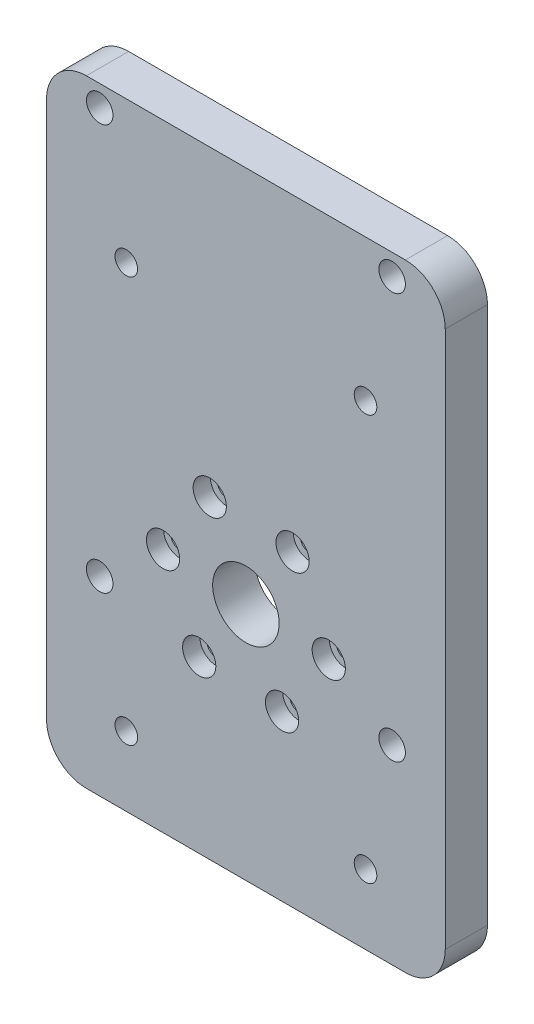
SolidWorks part; units mm, degrees
material "Aleación 6061"
ref_plane "Alzado" through (0, 0, 0) normal (0, 0, 1) x (1, 0, 0)
ref_plane "Planta" through (0, 0, 0) normal (0, 1, 0) x (1, 0, 0)
ref_plane "Vista lateral" through (0, 0, 0) normal (1, 0, 0) x (0, 0, -1)
ref_plane "Plano_xJ3" through (152.4, 0, 0) normal (1, 0, 0) x (0, 0, -1)
ref_plane "Plano_zJ5" through (0, 0, 336.55) normal (0, 0, 1) x (1, 0, 0)
ref_axis "Eje_J4" through (152.4, 0, 276.2675) along (0, 0, -1)
ref_axis "Eje_J5" through (152.4, -19.6438, 336.55) along (0, 1, 0)
sketch "Croquis13" plane through (0, 0, 0) normal (0, 0, 1) x (1, 0, 0)
  line L0 (128.4, -36) -> (176.4, -36)
  line L1 (182.4, -30) -> (182.4, 50.875)
  line L2 (176.4, 56.875) -> (128.4, 56.875)
  line L3 (122.4, 50.875) -> (122.4, -30)
  arc A0 (176.4, -36) -> (182.4, -30) centre (176.4, -30) ccw
  arc A1 (182.4, 50.875) -> (176.4, 56.875) centre (176.4, 50.875) ccw
  arc A2 (128.4, 56.875) -> (122.4, 50.875) centre (128.4, 50.875) ccw
  arc A3 (122.4, -30) -> (128.4, -36) centre (128.4, -30) ccw
  dimension "D1" = 6
  dimension "D2" = 6
  dimension "D3" = 6
  dimension "D4" = 6
  dimension "D5" = 128.4
  dimension "D6" = 36
  dimension "D7" = 176.4
  dimension "D8" = 36
  dimension "D9" = 182.4
  dimension "D10" = 30
  dimension "D11" = 182.4
  dimension "D12" = 50.875
  dimension "D13" = 176.4
  dimension "D14" = 56.875
  dimension "D15" = 128.4
  dimension "D16" = 56.875
  dimension "D17" = 122.4
  dimension "D18" = 50.875
  dimension "D19" = 122.4
  dimension "D20" = 30
extrude "Disco_1-4in" add sketch "Croquis13" along normal blind 6.35 from offset 269.6
sketch "Croquis14" plane through (0, 0, 0) normal (0, 0, 1) x (1, 0, 0)
  circle A0 centre (159.426, 10.3385) radius 1.45
  circle A1 centre (146.9596, 11.254) radius 1.45
  circle A2 centre (139.9336, 0.9155) radius 1.45
  circle A3 centre (145.374, -10.3385) radius 1.45
  circle A4 centre (157.8404, -11.254) radius 1.45
  circle A5 centre (164.8664, -0.9155) radius 1.45
  circle A6 centre (152.4, 0) radius 5
  circle A7 centre (134.4, 35.525) radius 1.25
  circle A8 centre (134.4, -25.525) radius 1.25
  circle A9 centre (170.4, 35.525) radius 1.25
  circle A10 centre (170.4, -25.525) radius 1.25
  circle A11 centre (130.4, 53.7) radius 2
  circle A12 centre (130.4, -7.35) radius 2
  circle A13 centre (174.4, 53.7) radius 2
  circle A14 centre (174.4, -7.35) radius 2
  dimension "D1" = 2.9
  dimension "D2" = 2.9
  dimension "D3" = 2.9
  dimension "D4" = 2.9
  dimension "D5" = 2.9
  dimension "D6" = 2.9
  dimension "D7" = 10
  dimension "D8" = 2.5
  dimension "D9" = 2.5
  dimension "D10" = 2.5
  dimension "D11" = 2.5
  dimension "D12" = 4
  dimension "D13" = 4
  dimension "D14" = 4
  dimension "D15" = 4
  dimension "D16" = 159.426
  dimension "D17" = 10.3385
  dimension "D18" = 146.9596
  dimension "D19" = 11.254
  dimension "D20" = 139.9336
  dimension "D21" = 0.9155
  dimension "D22" = 145.374
  dimension "D23" = 10.3385
  dimension "D24" = 157.8404
  dimension "D25" = 11.254
  dimension "D26" = 164.8664
  dimension "D27" = 0.9155
  dimension "D28" = 152.4
  dimension "D29" = 134.4
  dimension "D30" = 35.525
  dimension "D31" = 134.4
  dimension "D32" = 25.525
  dimension "D33" = 170.4
  dimension "D34" = 35.525
  dimension "D35" = 170.4
  dimension "D36" = 25.525
  dimension "D37" = 130.4
  dimension "D38" = 53.7
  dimension "D39" = 130.4
  dimension "D40" = 7.35
  dimension "D41" = 174.4
  dimension "D42" = 53.7
  dimension "D43" = 174.4
  dimension "D44" = 7.35
extrude "Barrenos_M4_escuadras_pasadores" cut sketch "Croquis14" along normal blind 6.35 from offset 269.6
sketch "Croquis15" plane through (0, 0, 0) normal (0, 0, 1) x (1, 0, 0)
  circle A0 centre (159.426, 10.3385) radius 2.5
  circle A1 centre (146.9596, 11.254) radius 2.5
  circle A2 centre (139.9336, 0.9155) radius 2.5
  circle A3 centre (145.374, -10.3385) radius 2.5
  circle A4 centre (157.8404, -11.254) radius 2.5
  circle A5 centre (164.8664, -0.9155) radius 2.5
  dimension "D1" = 5
  dimension "D2" = 5
  dimension "D3" = 5
  dimension "D4" = 5
  dimension "D5" = 5
  dimension "D6" = 5
  dimension "D7" = 159.426
  dimension "D8" = 10.3385
  dimension "D9" = 146.9596
  dimension "D10" = 11.254
  dimension "D11" = 139.9336
  dimension "D12" = 0.9155
  dimension "D13" = 145.374
  dimension "D14" = 10.3385
  dimension "D15" = 157.8404
  dimension "D16" = 11.254
  dimension "D17" = 164.8664
  dimension "D18" = 0.9155
extrude "Refrentado_M2-5" cut sketch "Croquis15" along normal blind 2.6 from offset 273.35
sketch "Croquis16" plane through (0, 0, 0) normal (0, 0, 1) x (1, 0, 0)
  circle A0 centre (134.4, 35.525) radius 1.7
  circle A1 centre (134.4, -25.525) radius 1.7
  circle A2 centre (170.4, 35.525) radius 1.7
  circle A3 centre (170.4, -25.525) radius 1.7
  dimension "D1" = 3.4
  dimension "D2" = 3.4
  dimension "D3" = 3.4
  dimension "D4" = 3.4
  dimension "D5" = 134.4
  dimension "D6" = 35.525
  dimension "D7" = 134.4
  dimension "D8" = 25.525
  dimension "D9" = 170.4
  dimension "D10" = 35.525
  dimension "D11" = 170.4
  dimension "D12" = 25.525
extrude "Paso_M3_escuadras_tuerca" cut sketch "Croquis16" along normal blind 6.35 from offset 269.6
